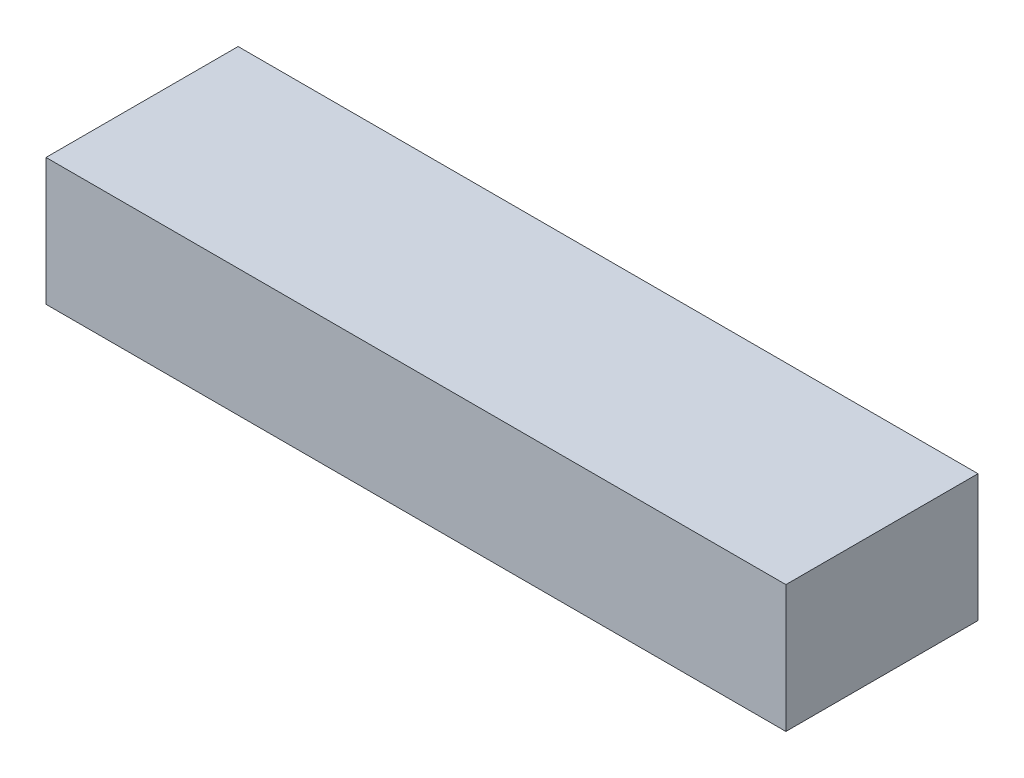
SolidWorks part; units mm, degrees
ref_plane "Front Plane" through (0, 0, 0) normal (0, 0, 1) x (1, 0, 0)
ref_plane "Top Plane" through (0, 0, 0) normal (0, 1, 0) x (1, 0, 0)
ref_plane "Right Plane" through (0, 0, 0) normal (1, 0, 0) x (0, 0, -1)
sketch "Sketch1" plane through (0, 0, 0) normal (0, 1, 0) x (1, 0, 0)
  line L1 (570, -148) -> (-570, -148)
  line L2 (570, -148) -> (570, 148)
  line L3 (570, 148) -> (-570, 148)
  line L4 (-570, -148) -> (-570, 148)
  line L5 (570, -148) -> (-570, 148) construction
  line L6 (570, 148) -> (-570, -148) construction
  point P0 (0, 0)
  dimension "D1" = 1140
  dimension "D2" = 296
extrude "Boss-Extrude1" add sketch "Sketch1" along normal blind 196
equation "\"assembly\"= 0"
equation "\"thickness 1\"= 2"
equation "\"thickness 2\"= 3"
equation "\"connecting flange\"= 35"
equation "\"main\"= 0"
equation "\"main length\"= 1200"
equation "\"main width\"= 1200"
equation "\"divider panel distance offset\"= 296"
equation "\"side panel\"= 0"
equation "\"access hatch length\"= 600"
equation "\"access hatch width\"= 450"
equation "\"access hatch offset X\"= 100"
equation "\"access hatch offset Y\"= 100"
equation "\"side panel length\"= 1200"
equation "\"side panel width\"= 950"
equation "\"back panel\"= 0"
equation "\"back panel access hatch length\"= 1150"
equation "\"back panel access hatch width\"= 206"
equation "\"back panel access hatch flange\"= 40"
equation "\"drift eliminator\"= 0"
equation "\"drift eliminator size offset\"= 10"
equation "\"drift eliminator length\"= \"back panel access hatch length\" - \"drift eliminator size offset\""
equation "\"drift eliminator width\"= \"back panel access hatch width\" - \"drift eliminator size offset\""
equation "\"drift eliminator depth\"= \"divider panel distance offset\""
equation "\"sump\"= 0"
equation "\"D1@Boss-Extrude1\"=\"drift eliminator width\""
equation "\"D1@Sketch1\"=\"drift eliminator length\""
equation "\"D2@Sketch1\"=\"drift eliminator depth\""
